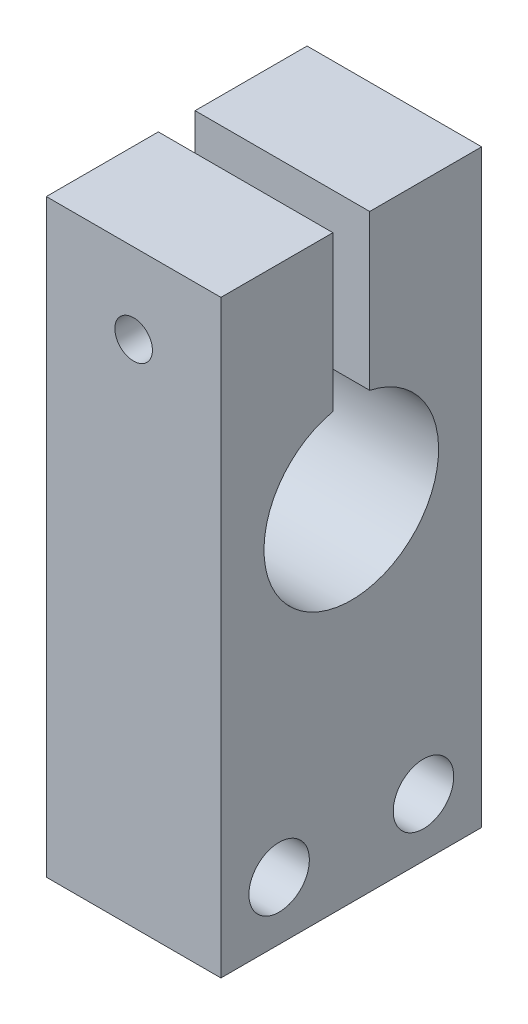
SolidWorks part; units mm, degrees
material "6061 Alloy"
ref_plane "Front Plane" through (0, 0, 0) normal (0, 0, 1) x (1, 0, 0)
ref_plane "Top Plane" through (0, 0, 0) normal (0, 1, 0) x (1, 0, 0)
ref_plane "Right Plane" through (0, 0, 0) normal (1, 0, 0) x (0, 0, -1)
ref_plane "Plane1" through (4.7625, 0, 0) normal (1, 0, 0) x (0, 0, -1)
sketch "Sketch1" plane through (4.7625, 0, 0) normal (1, 0, 0) x (0, 0, -1)
  line L0 (15.875, -19.05) -> (15.875, 13.1064)
  line L1 (15.875, 13.1064) -> (-15.875, 13.1064)
  line L2 (-15.875, 13.1064) -> (-15.875, -19.05)
  line L3 (-15.875, -19.05) -> (15.875, -19.05)
  dimension "D1" = 31.75
  dimension "D2" = 32.1564
  dimension "D3" = 13.1064
  dimension "D4" = 15.875
extrude "Boss-Extrude1" add sketch "Sketch1" against normal blind 9.525
sketch "Sketch2" plane through (-4.7625, 0, 0) normal (-1, 0, 0) x (0, 0, 1)
  line L0 (-7.112, -19.05) -> (-7.112, 13.1064)
  line L1 (-7.112, 13.1064) -> (-15.875, 13.1064)
  line L2 (-15.875, 13.1064) -> (-15.875, -19.05)
  line L3 (-15.875, -19.05) -> (-7.112, -19.05)
  line L4 (15.875, -19.05) -> (-15.875, -19.05) construction
  line L5 (-15.875, 13.1064) -> (15.875, 13.1064) construction
  line L6 (-15.875, -19.05) -> (-15.875, 13.1064) construction
  dimension "D1" = 8.763
extrude "Cut-Extrude1" cut sketch "Sketch2" against normal through all
sketch "Sketch3" plane through (-4.7625, 0, 0) normal (-1, 0, 0) x (0, 0, 1)
  line L0 (1.0033, 13.1064) -> (-1.0033, 13.1064)
  line L1 (-1.0033, 13.1064) -> (-1.0033, 4.6556)
  line L2 (1.0033, 4.6556) -> (1.0033, 13.1064)
  line L3 (-7.112, -19.05) -> (-7.112, 13.1064) construction
  line L4 (-7.112, 13.1064) -> (15.875, 13.1064) construction
  arc A0 (-1.0033, 4.6556) -> (1.0033, 4.6556) centre (0, 0) cw
  dimension "D1" = 4.7625
  dimension "D2" = 6.1087
  dimension "D3" = 7.112
  dimension "D4" = 8.4508
extrude "Cut-Extrude2" cut sketch "Sketch3" against normal through all
sketch "Sketch4" plane through (-4.7625, 0, 0) normal (-1, 0, 0) x (0, 0, 1)
  line L0 (7.112, -19.0536) -> (15.875, -19.0536)
  line L1 (15.875, -19.0536) -> (15.875, 13.1064)
  line L2 (15.875, 13.1064) -> (7.112, 13.1064)
  line L3 (7.112, 13.1064) -> (7.112, -19.0536)
  line L4 (1.0033, 4.6556) -> (1.0033, 13.1064) construction
  line L5 (1.0033, 13.1064) -> (15.875, 13.1064) construction
  dimension "D1" = 6.1087
  dimension "D2" = 14.8717
  dimension "D3" = 32.16
extrude "Cut-Extrude3" cut sketch "Sketch4" against normal through all
sketch "Sketch5" plane through (0, 0, 0) normal (0, 0, 1) x (1, 0, 0)
  line L0 (-4.7625, 4.7625) -> (-4.7625, 0)
  line L1 (-4.7625, 0) -> (4.7625, 0)
  line L2 (4.7625, 0) -> (4.7625, 4.7625)
  line L3 (4.7625, 4.7625) -> (-4.7625, 4.7625)
  line L4 (-4.7625, 0) -> (4.7625, 0) construction
  dimension "D1" = 4.7625
  dimension "D2" = 4.7625
  dimension "D3" = 4.7625
revolve "Cut-Revolve1" cut sketch "Sketch5" angle 360 about L4 reverse direction yes
hole_wizard "M2.5x0.45 Tapped Hole1" positions "Sketch7" profile "Sketch6" tap size "M2.5x0.45" standard "ANSI Metric" end condition up to next
sketch "Sketch7" plane through (0, 0, 7.112) normal (0, 0, -1) x (-1, 0, 0)
  point P0 (0, 8.7376)
sketch "Sketch6" plane through (0, 8.7376, 7.112) normal (1, 0, 0) x (0, -1, 0)
  line L0 (0, 0) -> (0, 6.1087)
  line L1 (0, 6.1087) -> (1.025, 6.1087)
  line L2 (1.025, 6.1087) -> (1.025, 0)
  line L5 (1.025, 0) -> (0, 0)
  line L11 (0, -6.35) -> (0, 107.95) construction
  dimension "Thru Tap Drill Dia." = 2.05
  dimension "Thru Tap Drill Depth" = 6.1087
hole_wizard "CBORE for M2.5 Hex Head Machine Screw1" positions "Sketch9" profile "Sketch8" counterbore size "M2.5" standard "ANSI Metric" end condition up to next
sketch "Sketch9" plane through (0, 0, -7.112) normal (0, 0, -1) x (-1, 0, 0)
  point P0 (0, 8.7376)
sketch "Sketch8" plane through (0, 8.7376, -7.112) normal (1, 0, 0) x (0, 1, 0)
  line L0 (0, 0) -> (0, 6.1087)
  line L1 (0, 6.1087) -> (1.55, 6.1087)
  line L3 (1.55, 6.1087) -> (1.55, 2.1)
  line L4 (1.55, 2.1) -> (3.64, 2.1)
  line L5 (3.64, 2.1) -> (3.64, 0)
  line L7 (3.64, 0) -> (0, 0)
  line L11 (0, -6.35) -> (0, 107.95) construction
  dimension "Thru Hole Dia." = 3.1
  dimension "Thru Hole Depth" = 6.1087
  dimension "C'Bore Dia." = 7.28
  dimension "C'Bore Depth" = 2.1
hole_wizard "M4x0.7 Tapped Hole1" positions "Sketch11" profile "Sketch10" tap size "M4x0.7" standard "ANSI Metric" end condition through all
sketch "Sketch11" plane through (4.7625, -17.4625, 0) normal (-1, 0, 0) x (0, 1, 0)
  line L3 (-1.5875, -7.112) -> (-1.5875, 7.112) construction
  line L4 (-1.5875, 7.112) -> (30.5689, 7.112) construction
  line L5 (30.5689, -7.112) -> (-1.5875, -7.112) construction
  point P2 (1.5875, 3.937)
  point P4 (1.5875, -3.937)
  dimension "D1" = 3.175
  dimension "D2" = 3.175
  dimension "D3" = 3.175
sketch "Sketch10" plane through (4.7625, -15.875, -3.937) normal (0, 1, 0) x (0, 0, -1)
  line L0 (0, 0) -> (0, 9.525)
  line L1 (0, 9.525) -> (1.65, 9.525)
  line L2 (1.65, 9.525) -> (1.65, 0)
  line L5 (1.65, 0) -> (0, 0)
  line L11 (0, -6.35) -> (0, 107.95) construction
  dimension "Thru Tap Drill Dia." = 3.3
  dimension "Thru Tap Drill Depth" = 9.525
